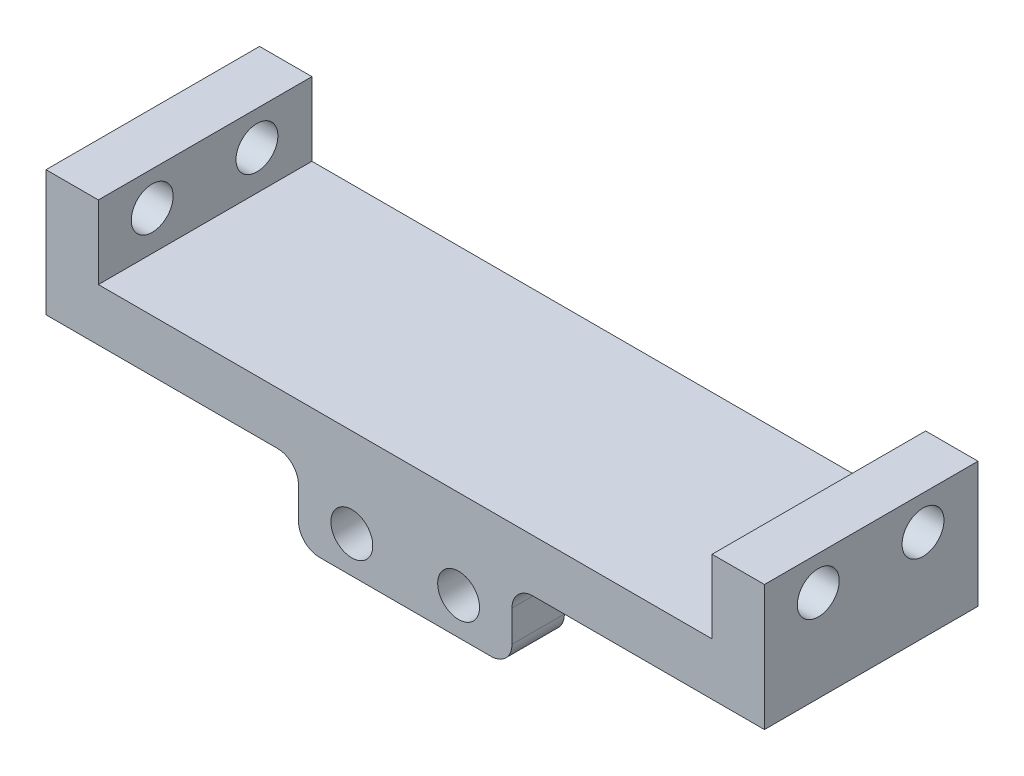
SolidWorks part; units mm, degrees
ref_plane "Front" through (0, 0, 0) normal (0, 0, 1) x (1, 0, 0)
ref_plane "Top" through (0, 0, 0) normal (0, 1, 0) x (1, 0, 0)
ref_plane "Right" through (0, 0, 0) normal (1, 0, 0) x (0, 0, -1)
sketch "Sketch1" plane through (0, 0, 0) normal (0, 1, 0) x (1, 0, 0)
  line L1 (0, 0) -> (68.6, 0)
  line L2 (0, 0) -> (0, 20.3898)
  line L3 (0, 20.3898) -> (68.6, 20.3898)
  line L4 (68.6, 0) -> (68.6, 20.3898)
  dimension "D1" = 68.6
  dimension "D2" = 20.3898
extrude "bracketBase" add sketch "Sketch1" along normal blind 5
sketch "Sketch2" plane through (0, 0, 0) normal (-1, 0, 0) x (0, 0, 1)
  line L0 (0, 5) -> (0, 0) construction
  line L1 (-20.3898, 0) -> (0, 0)
  line L2 (-20.3898, 0) -> (-20.3898, 12)
  line L3 (-20.3898, 12) -> (0, 12)
  line L4 (0, 0) -> (0, 12)
  line L5 (-20.3898, 5) -> (0, 5) construction
  dimension "D1" = 7
extrude "legMountingTab" add sketch "Sketch2" against normal blind 5
sketch "Sketch3" plane through (5, 0, 0) normal (1, 0, 0) x (0, 0, -1)
  line L0 (20.3898, 12) -> (20.3898, 5) construction
  line L1 (0, 12) -> (20.3898, 12) construction
  circle A0 centre (15.1398, 8.75) radius 2
  circle A1 centre (5.1398, 8.75) radius 2
  dimension "D1" = 4
  dimension "D2" = 5.25
  dimension "D3" = 3.25
  dimension "D4" = 10
extrude "legMountingHoles" cut sketch "Sketch3" against normal blind 5
ref_plane "Plane1" through (34.3, 0, 0) normal (-1, 0, 0) x (0, 0, 1)
mirror "legMountingHoles2" about plane through (34.3, 0, 0) normal (-1, 0, 0) of "legMountingHoles", "legMountingTab"
sketch "Sketch4" plane through (0, 0, 0) normal (0, 0, 1) x (1, 0, 0)
  line L0 (0, 0) -> (68.6, 0) construction
  line L1 (44.4949, 0) -> (24.1051, 0)
  line L2 (44.4949, 0) -> (44.4949, -7)
  line L3 (44.4949, -7) -> (24.1051, -7)
  line L4 (24.1051, 0) -> (24.1051, -7)
  point P4 (34.3, 0)
  point P7 (34.3, 0)
  dimension "D1" = 7
  dimension "D2" = 20.3898
extrude "arduinoMountingTab" add sketch "Sketch4" against normal blind 5
sketch "Sketch5" plane through (0, 0, 0) normal (0, 0, 1) x (1, 0, 0)
  line L2 (34.3, -7) -> (34.3, 5) construction
  line L3 (24.1051, -7) -> (44.4949, -7) construction
  line L4 (5, 5) -> (63.6, 5) construction
  line L5 (44.4949, -3.5) -> (34.3, -3.5) construction
  line L8 (44.4949, -7) -> (44.4949, 0) construction
  circle A0 centre (39.3974, -3.5) radius 2
  circle A1 centre (29.2026, -3.5) radius 2
  dimension "D1" = 4
extrude "arduinoMountingHoles" cut sketch "Sketch5" against normal blind 5
fillet "Fillet1" radius 2 4 edges at (24.1051, -7, -2.5) (44.4949, -7, -2.5) (44.4949, 0, -2.5) (24.1051, 0, -2.5)
